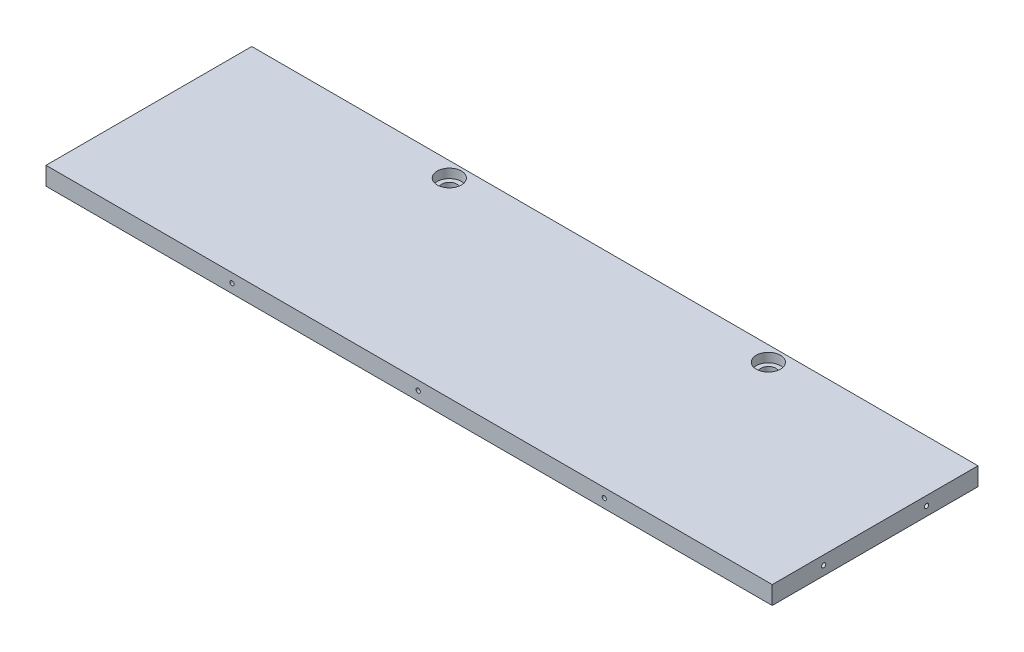
SolidWorks part; units mm, degrees
ref_plane "前视基准面" through (0, 0, 0) normal (0, 0, 1) x (1, 0, 0)
ref_plane "上视基准面" through (0, 0, 0) normal (0, 1, 0) x (1, 0, 0)
ref_plane "右视基准面" through (0, 0, 0) normal (1, 0, 0) x (0, 0, -1)
other "Configuration Table"
sketch "草图1" plane through (0, 0, 0) normal (0, 1, 0) x (1, 0, 0)
  line L1 (-60, -17) -> (60, -17)
  line L2 (-60, -17) -> (-60, 17)
  line L3 (-60, 17) -> (60, 17)
  line L4 (60, -17) -> (60, 17)
  line L5 (-60, -17) -> (60, 17) construction
  line L6 (-60, 17) -> (60, -17) construction
  point P0 (0, 0)
  dimension "D1" = 120
  dimension "D5" = 34
extrude "凸台-拉伸1" add sketch "草图1" along normal blind 3 contours L3 L4 L1 L2
sketch "草图2" plane through (0, 3, 0) normal (0, 1, 0) x (1, 0, 0)
  circle A2 centre (-24.8571, 14.5) radius 1.25
  circle A3 centre (-24.8571, 14.5) radius 2
  circle A8 centre (27.8571, 14.5) radius 1.25
  circle A9 centre (27.8571, 14.5) radius 2
  point P0 (0, 0)
  dimension "D1" = 2.5
  dimension "D2" = 4
extrude "切除-拉伸1" cut sketch "草图2" against normal through all contours A8 | A2
extrude "切除-拉伸2" cut sketch "草图2<3>" against normal blind 1.5 contours A3 | A9
sketch "草图2<3>" plane through (0, 3, 0) normal (0, 1, 0) x (1, 0, 0) same geometry as "草图2"
sketch "草图3" plane through (60, 0, 0) normal (1, 0, 0) x (0, 0, -1)
  circle A0 centre (-8.5, 1.5) radius 0.35
  circle A1 centre (8.5, 1.5) radius 0.35
  point P4 (0, 0)
  dimension "D1" = 0.7
extrude "切除-拉伸3" cut sketch "草图3" against normal blind 3
sketch "草图4" plane through (0, 0, 17) normal (0, 0, 1) x (1, 0, 0)
  circle A0 centre (-29.25, 1.5) radius 0.35
  circle A1 centre (1.5, 1.5) radius 0.35
  circle A2 centre (32.25, 1.5) radius 0.35
  point P6 (0, 0)
  dimension "D1" = 0.7
extrude "切除-拉伸4" cut sketch "草图4" against normal blind 3
